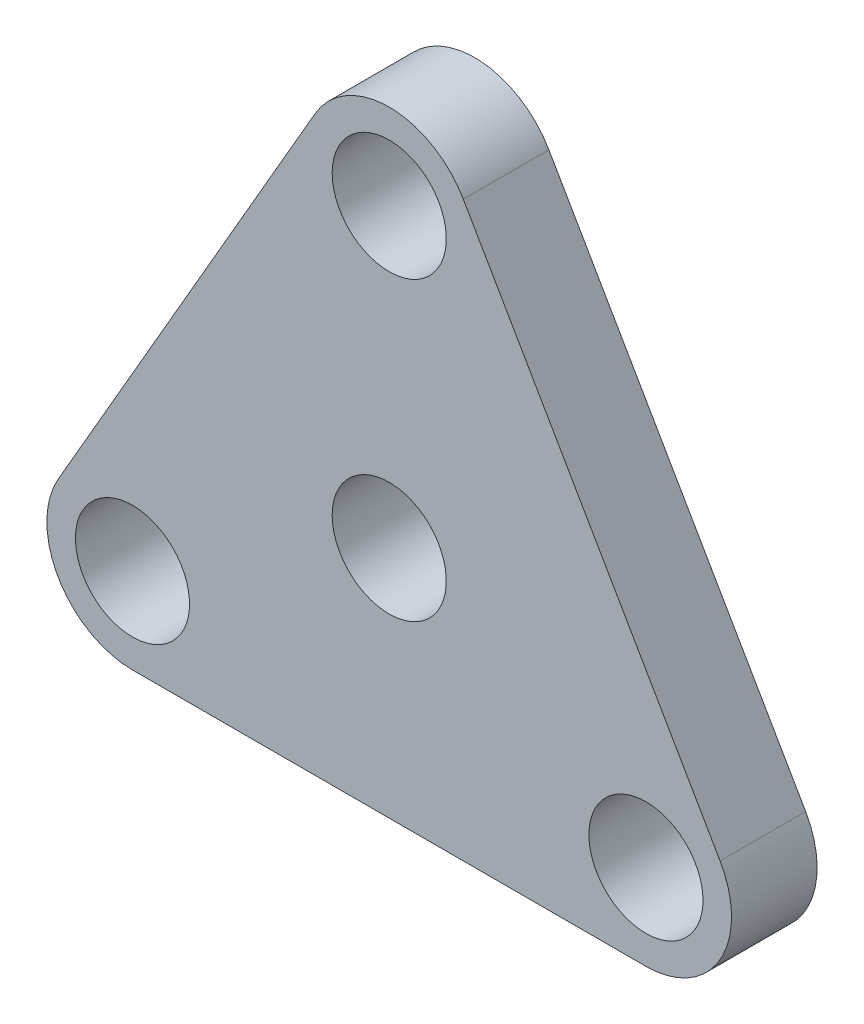
SolidWorks part; units mm, degrees
material "AISI 1020"
ref_plane "Front Plane" through (0, 0, 0) normal (0, 0, 1) x (1, 0, 0)
ref_plane "Top Plane" through (0, 0, 0) normal (0, 1, 0) x (1, 0, 0)
ref_plane "Right Plane" through (0, 0, 0) normal (1, 0, 0) x (0, 0, -1)
sketch "Sketch1" plane through (0, 0, 0) normal (0, 0, 1) x (1, 0, 0)
  line L0 (0, 13.5863) -> (0, -12.6778) construction
  line L1 (-28.575, -16.4978) -> (28.575, -16.4978) construction
  line L2 (-28.575, -16.4978) -> (0, 32.9956) construction
  line L3 (0, 32.9956) -> (28.575, -16.4978) construction
  line L4 (-9.2855, 0) -> (9.7088, 0) construction
  line L5 (14.2875, 8.2489) -> (-28.575, -16.4978) construction
  line L6 (-14.2875, 8.2489) -> (28.575, -16.4978) construction
  line L7 (-8.2489, 37.7581) -> (-36.8239, -11.7353)
  line L8 (-28.575, -26.0228) -> (28.575, -26.0228)
  line L9 (36.8239, -11.7353) -> (8.2489, 37.7581)
  circle A0 centre (0, 0) radius 6.35
  arc A1 (8.2489, 37.7581) -> (-8.2489, 37.7581) centre (0, 32.9956) ccw
  arc A2 (-36.8239, -11.7353) -> (-28.575, -26.0228) centre (-28.575, -16.4978) ccw
  arc A3 (28.575, -26.0228) -> (36.8239, -11.7353) centre (28.575, -16.4978) ccw
  circle A4 centre (-28.575, -16.4978) radius 6.35
  circle A5 centre (0, 32.9956) radius 6.35
  circle A6 centre (28.575, -16.4978) radius 6.35
  point P12 (0, 0)
  dimension "D1" = 12.7
  dimension "D3" = 19.05
  dimension "D4" = 12.7
  dimension "D2" = 57.15
extrude "Boss-Extrude1" add sketch "Sketch1" along normal blind 9.525
